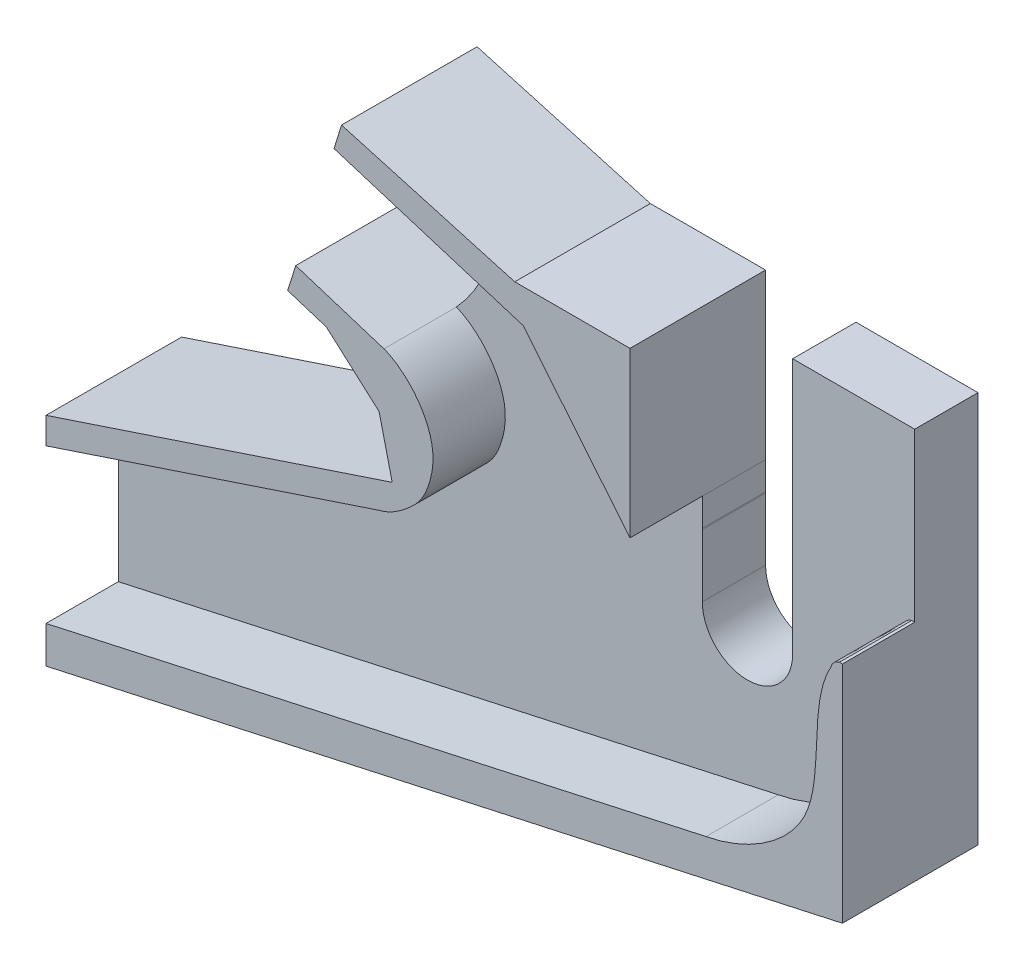
SolidWorks part; units mm, degrees
note: The reader was unsure of these and kept them because the rebuilt part matched: shared geometry of "Sketch2<5>".
ref_plane "Front Plane" through (0, 0, 0) normal (0, 0, 1) x (1, 0, 0)
ref_plane "Top Plane" through (0, 0, 0) normal (0, 1, 0) x (1, 0, 0)
ref_plane "Right Plane" through (0, 0, 0) normal (1, 0, 0) x (0, 0, -1)
sketch "Sketch2" plane through (0, 0, 0) normal (0, 0, 1) x (1, 0, 0)
  line L0 (84.9746, 166.5371) -> (89.9416, 180.6908) construction
  line L6 (38.05, 121.9088) -> (119.3085, 139.8147)
  line L7 (88.0764, 182.0685) -> (99.076, 178.6563)
  line L11 (110.8955, 152.3458) -> (110.8955, 177.8471)
  line L12 (110.8955, 177.8471) -> (120.8955, 177.8471)
  line L13 (120.8955, 177.8471) -> (120.8955, 152.3458)
  line L14 (99.076, 178.6563) -> (110.8955, 164.2219)
  line L16 (134.0571, 163.8909) -> (145.0614, 163.8909)
  line L17 (83.6787, 168.7282) -> (44.3019, 181.2181)
  line L21 (44.3019, 181.2181) -> (43.403, 178.3841)
  line L22 (43.403, 178.3841) -> (77.2981, 167.6329)
  line L23 (77.2981, 167.6329) -> (83.1349, 162.4624)
  line L24 (83.1349, 162.4624) -> (84.5894, 156.392)
  line L25 (84.5894, 156.392) -> (46.2859, 143.6615)
  line L28 (91.9869, 145.3747) -> (93.1811, 145.5579)
  line L29 (46.2859, 143.6615) -> (46.2859, 140.7384)
  line L30 (88.0764, 182.0685) -> (78.1511, 185.1475)
  line L31 (78.1511, 185.1475) -> (78.981, 187.8227)
  line L32 (78.981, 187.8227) -> (98.1451, 182.3849)
  line L33 (73.9172, 171.8244) -> (73.0183, 168.9904)
  line L34 (46.2859, 123.7237) -> (46.2859, 119.6347)
  line L35 (46.2859, 119.6347) -> (134.3963, 139.0504)
  line L36 (46.2859, 140.7384) -> (46.2859, 123.7237)
  line L42 (134.3938, 182.387) -> (38.7242, 182.3814)
  line L70 (38.7247, 172.8763) -> (38.05, 121.9088)
  line L72 (111.8833, 113.2591) -> (64.5833, 94.1879) construction
  line L73 (81.094, 168.8464) -> (38.4911, 155.2267)
  line L74 (120.8952, 168.847) -> (120.8944, 182.3863)
  line L75 (110.8952, 168.8464) -> (110.8944, 182.3857)
  line L85 (38.7247, 172.8763) -> (38.7242, 182.3814)
  line L87 (110.8963, 149.1) -> (120.8963, 149.1005)
  line L89 (120.8952, 168.847) -> (120.8963, 149.1005)
  line L91 (58.3065, 97.627) -> (58.7427, 93.6841)
  line L93 (83.1349, 152.9854) -> (38.2057, 138.0528)
  line L95 (115.8955, 154.1002) -> (115.895, 161.0793)
  line L96 (110.8952, 168.8464) -> (110.8963, 149.1)
  line L97 (110.8952, 168.8464) -> (120.8952, 168.847)
  line L98 (110.8952, 168.8464) -> (120.8952, 168.847)
  line L100 (134.3982, 107.7265) -> (134.3938, 182.387)
  circle A0 centre (115.8955, 154.1002) radius 5
  circle A7 centre (115.895, 161.0793) radius 5
  circle A8 centre (64.9473, 94.5712) radius 6.2677
  circle A9 centre (112.0025, 113.9752) radius 6.25
  circle A10 centre (115.8955, 154.1002) radius 5
  circle A11 centre (64.9473, 94.5712) radius 3
  circle A12 centre (112.0025, 113.9752) radius 3
  spline S0 degree 2 poles (83.6787, 168.7282) (88.7746, 174.3121) (88.0764, 182.0685) knots 0 0 0 1 1 1
  spline S1 degree 3 poles (119.3085, 139.8147) (123.464, 140.563) (134.0829, 146.5279) (130.5567, 158.4614) (133.1087, 162.9171) knots 0 0 0 0 0.463456 1 1 1 1
  spline S2 degree 2 poles (133.1087, 162.9171) (133.3287, 163.6952) (134.0571, 163.8909) knots 0 0 0 1 1 1
  spline S16 degree 3 poles (83.1349, 152.9854) (84.1749, 153.2307) (85.8407, 154.2833) (87.7956, 156.0948) (88.8368, 158.5149) (89.6098, 162.7286) (86.4985, 167.7286) (82.7249, 169.2911) (81.094, 168.8464) knots 0 0 0 0 0.137401 0.255124 0.340172 0.476919 0.801614 1 1 1 1
  point P36 (88.0764, 182.0685)
  point P39 (98.8078, 178.7907)
  point P40 (110.8949, 164.2219)
  point P41 (99.076, 178.6563)
extrude "Boss-Extrude1" add sketch "Sketch2" along normal blind 7
extrude "Boss-Extrude3" add sketch "Sketch2<5>" along normal blind 15 contours L96 L75 L42 L30 L7 L14 | L42 L32 L31 L30 | L93 S16 L17 L73 L23 L24 L25 L29 | S16 L17 L33 L22 L73 | S2 S1 L6 L34 L35 L100 L16
sketch "Sketch2<5>" plane through (0, 0, 0) normal (0, 0, 1) x (1, 0, 0) same geometry as "Sketch2"
